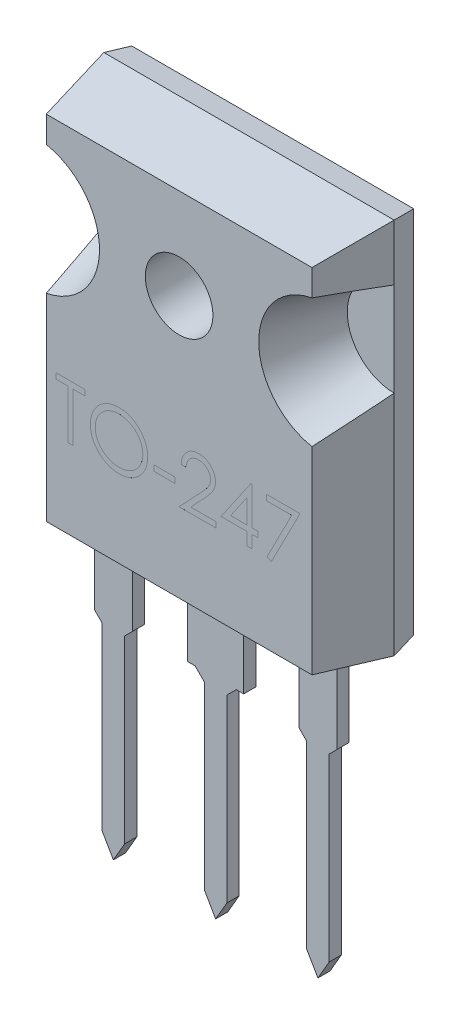
SolidWorks part; units mm, degrees
ref_plane "Front Plane" through (0, 0, 0) normal (0, 0, 1) x (1, 0, 0)
ref_plane "Top Plane" through (0, 0, 0) normal (0, 1, 0) x (1, 0, 0)
ref_plane "Right Plane" through (0, 0, 0) normal (1, 0, 0) x (0, 0, -1)
sketch "Sketch1" plane through (0, 0, 0) normal (0, 0, 1) x (1, 0, 0)
  line L1 (-7.75, 10.075) -> (7.75, 10.075)
  line L2 (-7.75, 10.075) -> (-7.75, -10.075)
  line L3 (-7.75, -10.075) -> (7.75, -10.075)
  line L4 (7.75, 10.075) -> (7.75, -10.075)
  line L5 (-7.75, 10.075) -> (7.75, -10.075) construction
  line L6 (-7.75, -10.075) -> (7.75, 10.075) construction
  point P0 (0, 0)
  dimension "D1" = 15.5
  dimension "D2" = 20.15
extrude "Boss-Extrude1" add sketch "Sketch1" against normal blind 1.27 draft 10 and the other way blind 3.73 draft 10
sketch "Sketch2" plane through (0, 0, 0) normal (0, 0, 1) x (1, 0, 0)
  line L0 (7.75, 10.075) -> (-7.75, 10.075) construction
  line L1 (-5.25, 7.4139) -> (-5.25, 0.8413) construction
  line L2 (-7.75, 10.075) -> (-7.75, -10.075) construction
  line L3 (0, 14.1994) -> (0, -3.2617) construction
  line L4 (7.75, -10.075) -> (7.75, 10.075) construction
  circle A0 centre (0, 4.565) radius 1.805 construction
  circle A1 centre (-7.75, 4.575) radius 2.5
  circle A2 centre (7.75, 4.575) radius 2.5
  dimension "D1" = 5.51
  dimension "D2" = 3.61
  dimension "D3" = 5.5
  dimension "D4" = 5
  dimension "D5" = 2.5
  dimension "D6" = 7.75
extrude "Cut-Extrude1" cut sketch "Sketch2" along normal up to surface (3.73 mm away) draft 15
sketch "Sketch4" plane through (0, 0, 0) normal (0, 0, 1) x (1, 0, 0)
  line L0 (7.75, 10.075) -> (-7.75, 10.075) construction
  circle A0 centre (0, 4.565) radius 1.805
  dimension "D1" = 3.61
  dimension "D2" = 5.51
extrude "Cut-Extrude2" cut sketch "Sketch4" along normal through all both and the other way through all
sketch "Sketch5" plane through (0, 0, 0) normal (0, 1, 0) x (1, 0, 0)
  line L0 (-9.5483, -1.13) -> (8.845, -1.13) construction
  line L1 (7.5261, 1.27) -> (-7.5261, 1.27) construction
  line L2 (0, 2.9425) -> (0, -4.6836) construction
  line L3 (-6.47, -1.13) -> (-4.45, -1.13)
  line L4 (-6.47, -1.13) -> (-6.47, -1.78)
  line L5 (-6.47, -1.78) -> (-4.45, -1.78)
  line L6 (-4.45, -1.13) -> (-4.45, -1.78)
  line L7 (-5.46, -1.13) -> (-5.46, -1.78) construction
  line L8 (6.47, -1.13) -> (6.47, -1.78)
  line L9 (6.47, -1.13) -> (4.45, -1.13)
  line L10 (4.45, -1.13) -> (4.45, -1.78)
  line L11 (6.47, -1.78) -> (4.45, -1.78)
  line L13 (-1.5, -1.13) -> (1.5, -1.13)
  line L14 (-1.5, -1.13) -> (-1.5, -1.78)
  line L15 (-1.5, -1.78) -> (1.5, -1.78)
  line L16 (1.5, -1.13) -> (1.5, -1.78)
  point P21 (0, -1.13)
  dimension "D1" = 2.4
  dimension "D2" = 2.02
  dimension "D3" = 0.65
  dimension "D4" = 5.46
  dimension "D5" = 3
extrude "Boss-Extrude2" add sketch "Sketch5" against normal blind 14.07
sketch "Sketch6" plane through (0, 0, 1.78) normal (0, 0, 1) x (1, 0, 0)
  line L0 (1.5, -14.07) -> (-6.47, -14.07)
  line L1 (-6.47, -14.07) -> (-6.47, -11.9156)
  line L2 (-6.47, -14.07) -> (-6.47, -9.7611) construction
  line L3 (-6.47, -11.9156) -> (1.5, -11.9156)
  line L4 (1.5, -14.07) -> (1.5, -9.7611) construction
  line L5 (1.5, -11.9156) -> (1.5, -14.07)
extrude "Boss-Extrude3" add sketch "Sketch6" against normal up to surface (0.65 mm away) up to face at (-5.46, -11.9729, 1.13)
sketch "Sketch7" plane through (0, 0, -1.27) normal (0, 0, -1) x (-1, 0, 0)
  line L0 (-7.75, 10.075) -> (7.75, 10.075) construction
  line L1 (-5.9, 9.225) -> (5.9, 9.225)
  line L2 (-6.9, 8.225) -> (-6.9, -3.855)
  line L3 (-6.9, -3.855) -> (6.9, -3.855)
  line L4 (6.9, 8.225) -> (6.9, -3.855)
  line L5 (-6.9, 9.225) -> (6.9, -3.855) construction
  line L6 (-6.9, -3.855) -> (6.9, 9.225) construction
  line L7 (7.75, 7.075) -> (7.75, 2.075) construction
  circle A0 centre (0, 4.565) radius 1.805 construction
  circle A1 centre (0, 4.565) radius 1.805
  arc A2 (-6.9, 8.225) -> (-5.9, 9.225) centre (-5.9, 8.225) cw
  arc A3 (6.9, 8.225) -> (5.9, 9.225) centre (5.9, 8.225) ccw
  point P0 (0, 2.685)
  dimension "D4" = 1
  dimension "D1" = 13.08
  dimension "D2" = 0.85
  dimension "D3" = 0.85
extrude "Boss-Extrude4" add sketch "Sketch7" along normal blind 0.0001
sketch "Sketch8" plane through (0, 0, 1.78) normal (0, 0, 1) x (1, 0, 0)
  line L0 (-6.06, -14.07) -> (-6.06, -24.1858)
  line L1 (-6.47, -14.07) -> (1.5, -14.07) construction
  line L2 (-6.06, -24.1858) -> (-5.46, -25.225)
  line L3 (-5.46, -25.225) -> (-4.86, -24.1858)
  line L4 (-4.86, -24.1858) -> (-4.86, -14.07)
  line L5 (-7.75, -10.075) -> (7.75, -10.075) construction
  line L6 (-5.46, -9.7611) -> (-5.46, -27.3304) construction
  line L7 (-6.47, -9.7611) -> (-4.45, -9.7611) construction
  line L8 (0, -9.7611) -> (0, -26.1766) construction
  line L9 (-1.5, -9.7611) -> (1.5, -9.7611) construction
  line L10 (-6.06, -14.07) -> (-4.86, -14.07)
  line L11 (6.06, -14.07) -> (6.06, -24.1858)
  line L12 (6.06, -24.1858) -> (5.46, -25.225)
  line L13 (5.46, -25.225) -> (4.86, -24.1858)
  line L14 (4.86, -24.1858) -> (4.86, -14.07)
  line L15 (6.06, -14.07) -> (4.86, -14.07)
  line L16 (-0.6, -14.07) -> (-0.6, -24.1858)
  line L17 (-0.6, -24.1858) -> (0, -25.225)
  line L18 (0, -25.225) -> (0.6, -24.1858)
  line L19 (0.6, -24.1858) -> (0.6, -14.07)
  line L20 (-0.6, -14.07) -> (0.6, -14.07)
  point P28 (0, -14.07)
  dimension "D1" = 15.15
  dimension "D2" = 1.2
  dimension "D3" = 60
  dimension "D4" = 1.2
  dimension "D5" = 60
extrude "Boss-Extrude5" add sketch "Sketch8" against normal up to surface (0.65 mm away) up to face at (5.46, -11.9729, 1.13)
sketch "Sketch9" plane through (0, 0, 1.78) normal (0, 0, 1) x (1, 0, 0)
  line L0 (-1.5, -11.9156) -> (-1.5, -14.07)
  line L1 (0.6, -14.07) -> (1.5, -14.07) construction
  line L2 (-1.5, -11.9156) -> (-4.45, -11.9156)
  line L3 (-4.45, -11.9156) -> (-4.45, -14.07)
  line L4 (-4.45, -14.07) -> (-4.45, -14.32)
  line L5 (-4.45, -14.32) -> (-1.5, -14.32)
  line L6 (-1.5, -14.32) -> (-1.5, -14.07)
extrude "Cut-Extrude3" cut sketch "Sketch9" against normal blind 1
chamfer "Chamfer1" distance 0.5 angle 45 10 edges at (-4.86, -14.07, 1.455) (-6.06, -14.07, 1.455) (0.6, -14.07, 1.455) (-0.6, -14.07, 1.455) (6.06, -14.07, 1.455) (4.86, -14.07, 1.455) (-4.45, -14.07, 1.455) (-6.47, -14.07, 1.455) (6.47, -14.07, 1.455) (4.45, -14.07, 1.455)
sketch "Sketch10" plane through (0, 0, 3.73) normal (0, 0, 1) x (1, 0, 0)
  line L0 (-7.0923, -5.1918) -> (7.0923, -5.1918) construction
  line L1 (-7.0923, 1.1379) -> (-7.0923, -9.4173) construction
  line L2 (7.0923, -9.4173) -> (7.0923, 1.1379) construction
  text T0 "TO-247" font "Century Gothic" height in points 11
extrude "Cut-Extrude4" cut sketch "Sketch10" against normal blind 0.0001
